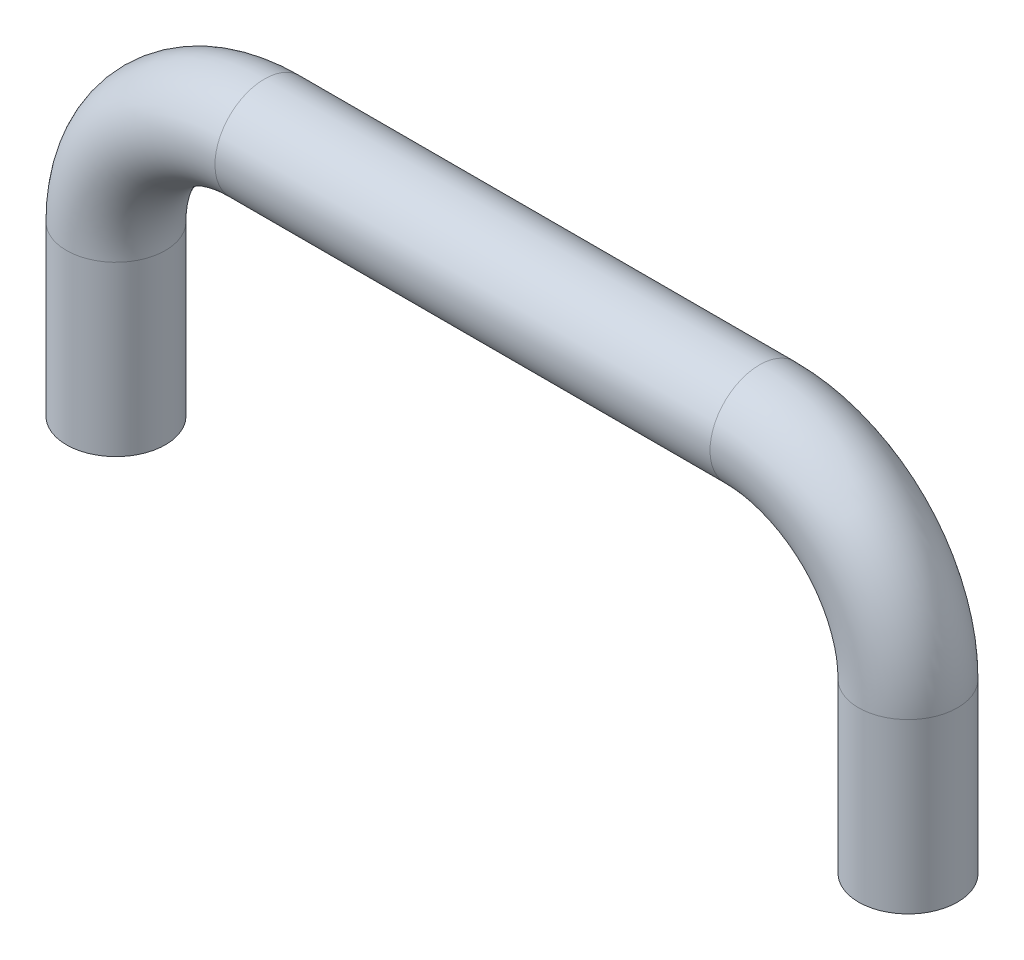
SolidWorks part; units mm, degrees
ref_plane "Front Plane" through (0, 0, 0) normal (0, 0, 1) x (1, 0, 0)
ref_plane "Top Plane" through (0, 0, 0) normal (0, 1, 0) x (1, 0, 0)
ref_plane "Right Plane" through (0, 0, 0) normal (1, 0, 0) x (0, 0, -1)
ref_axis "Axis_X" through (-49.5, 0, 0) along (1, 0, 0)
ref_axis "Axis_Y" through (0, 38.85, 0) along (0, -1, 0)
ref_axis "Axis_Z" through (0, 0, -5.5) along (0, 0, 1)
sketch "Sketch1" plane through (0, 0, 0) normal (0, 1, 0) x (1, 0, 0)
  line L0 (-40, 0) -> (0, 0) construction
  line L1 (0, 0) -> (40, 0) construction
  circle A0 centre (-40, 0) radius 5
  circle A1 centre (40, 0) radius 5 construction
  dimension "L" = 80
  dimension "D" = 10
sketch "Sketch2" plane through (0, 0, 0) normal (0, 0, 1) x (1, 0, 0)
  line L0 (-40, 0) -> (-40, 17)
  line L1 (-25, 32) -> (25, 32)
  line L2 (40, 17) -> (40, 0)
  line L3 (-25, 27) -> (25, 27) construction
  arc A0 (25, 32) -> (40, 17) centre (25, 17) cw
  arc A1 (-40, 17) -> (-25, 32) centre (-25, 17) cw
  point P8 (0, 32)
  dimension "KSS_2" = 15
  dimension "L" = 80
  dimension "H" = 27
  dimension "KSS_1" = 5
sweep "Sweep1" add profiles "Sketch1" path "Sketch2"
hole_wizard "Tap1" positions "Sketch4" profile "Sketch3" hole size "M4x0.7" standard "JIS"
sketch "Sketch4" plane through (0, 0, 0) normal (0, 1, 0) x (1, 0, 0)
  point P0 (-40, 0)
  point P3 (40, 0)
sketch "Sketch3" plane through (-40, 0, 0) normal (1, 0, 0) x (0, 0, -1)
  line L0 (0, 0) -> (0, 11.242)
  line L1 (0, 11.242) -> (2.067, 10)
  line L2 (2.067, 10) -> (2.067, 0)
  line L5 (2.067, 0) -> (0, 0)
  line L10 (0, 11.242) -> (-2.067, 10) construction
  line L11 (0, 0) -> (0, 11.242) construction
  dimension "HSD_1" = 4.134
  dimension "FIX_1" = 10
  dimension "Drill Angle" = 118
equation "\"KSS_1@Sketch2\"  = \"D@Sketch1\" / 2"
equation "\"KSS_2@Sketch2\" = 1.5 * \"D@Sketch1\""
